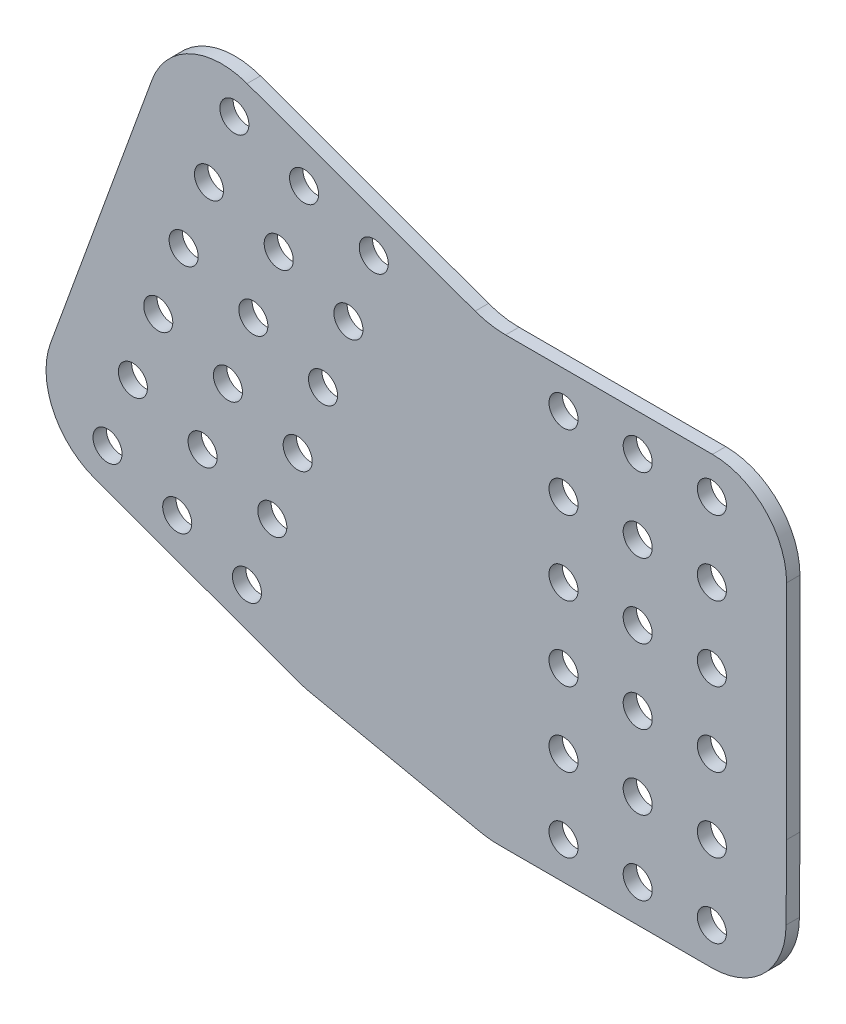
SolidWorks part; units mm, degrees
ref_plane "Front Plane" through (0, 0, 0) normal (0, 0, 1) x (1, 0, 0)
ref_plane "Top Plane" through (0, 0, 0) normal (0, 1, 0) x (1, 0, 0)
ref_plane "Right Plane" through (0, 0, 0) normal (1, 0, 0) x (0, 0, -1)
sketch "Sketch2" plane through (0, 0, 0) normal (0, 0, 1) x (1, 0, 0)
  line L0 (33.4302, 610.9533) -> (33.4302, 560.1533)
  line L1 (33.4302, 610.9533) -> (-17.3698, 610.9533)
  line L2 (-17.3698, 610.9533) -> (-70.8829, 630.4304)
  line L3 (-70.8829, 630.4304) -> (-88.2575, 582.694)
  line L4 (-88.2575, 582.694) -> (-40.5211, 565.3194)
  line L5 (-40.5211, 565.3194) -> (-17.3698, 560.1533)
  line L6 (-17.3698, 560.1533) -> (33.4302, 560.1533)
  line L7 (-70.8829, 630.4304) -> (-76.8499, 632.6022)
  line L8 (-76.8499, 632.6022) -> (-94.2245, 584.8659)
  line L9 (-94.2245, 584.8659) -> (-88.2575, 582.694)
  line L10 (-17.3698, 610.9533) -> (-17.3698, 560.1533)
  line L11 (-40.5211, 565.3194) -> (-23.1465, 613.0558)
  line L12 (33.4302, 610.9533) -> (39.7802, 610.9533)
  line L13 (39.7802, 610.9533) -> (39.7802, 560.1533)
  line L14 (39.7802, 560.1533) -> (33.4302, 560.1533)
  line L15 (-88.2575, 582.694) -> (-92.6011, 570.7599)
  line L16 (-66.5392, 642.3645) -> (-275.0347, 69.5279) construction
  line L17 (-92.6011, 570.7599) -> (-44.8648, 553.3853)
  line L18 (-18.8028, 624.9899) -> (-227.2983, 52.1533) construction
  line L19 (-44.8648, 553.3853) -> (-40.5211, 565.3194)
  line L20 (-17.3698, 560.1533) -> (-17.4643, 547.4533)
  line L21 (-17.4643, 610.9533) -> (-17.4643, -74.8467) construction
  line L22 (-17.4643, 547.4533) -> (33.3357, 547.4533)
  line L23 (33.3357, 610.9533) -> (33.3357, -74.8467) construction
  line L24 (33.3357, 547.4533) -> (33.4302, 560.1533)
  line L25 (-18.8028, 624.9899) -> (-66.5392, 642.3645) construction
  line L26 (-61.1206, 620.1197) -> (-65.4643, 608.1856) construction
  line L27 (-92.6011, 570.7599) -> (-96.9448, 558.8258)
  line L28 (-96.9448, 558.8258) -> (-49.2084, 541.4512)
  line L29 (-49.2084, 541.4512) -> (-44.8648, 553.3853)
  line L30 (-17.4643, 547.4533) -> (-17.4643, 534.7533)
  line L31 (-17.4643, 534.7533) -> (33.3357, 534.7533)
  line L32 (33.3357, 534.7533) -> (33.3357, 547.4533)
  line L33 (-49.2084, 541.4512) -> (-17.4643, 534.7533)
  line L34 (-61.1206, 620.1197) -> (-49.1865, 615.7761) construction
  line L35 (-57.8738, 591.9079) -> (-53.5302, 603.842) construction
  line L36 (-49.1865, 615.7761) -> (-37.2524, 611.4324) construction
  line L37 (-37.2524, 611.4324) -> (-41.5961, 599.4983) construction
  line L38 (-41.5961, 599.4983) -> (-45.9397, 587.5642) construction
  circle A25 centre (-49.1865, 615.7761) radius 2.4892 construction
  circle A26 centre (-61.1206, 620.1197) radius 2.4892 construction
  circle A27 centre (-49.1865, 615.7761) radius 2.4892
  circle A28 centre (-61.1206, 620.1197) radius 2.4892
  circle A29 centre (-37.2524, 611.4324) radius 2.4892 construction
  circle A30 centre (-50.2834, 575.6301) radius 2.4892 construction
  circle A31 centre (-74.1516, 584.3174) radius 2.4892 construction
  circle A32 centre (-62.2175, 579.9738) radius 2.4892 construction
  circle A33 centre (-54.627, 563.696) radius 2.4892 construction
  circle A34 centre (-66.5611, 568.0397) radius 2.4892 construction
  circle A35 centre (-78.4952, 572.3833) radius 2.4892 construction
  circle A36 centre (-37.2524, 611.4324) radius 2.4892
  circle A37 centre (-50.2834, 575.6301) radius 2.4892
  circle A38 centre (-74.1516, 584.3174) radius 2.4892
  circle A39 centre (-62.2175, 579.9738) radius 2.4892
  circle A40 centre (-54.627, 563.696) radius 2.4892
  circle A41 centre (-66.5611, 568.0397) radius 2.4892
  circle A42 centre (-78.4952, 572.3833) radius 2.4892
  circle A43 centre (-4.7643, 591.9033) radius 2.4892 construction
  circle A44 centre (7.9357, 591.9033) radius 2.4892 construction
  circle A45 centre (20.6357, 591.9033) radius 2.4892 construction
  circle A46 centre (20.6357, 604.6033) radius 2.4892 construction
  circle A47 centre (7.9357, 604.6033) radius 2.4892 construction
  circle A48 centre (-4.7643, 604.6033) radius 2.4892 construction
  circle A49 centre (-4.7643, 591.9033) radius 2.4892
  circle A50 centre (7.9357, 591.9033) radius 2.4892
  circle A51 centre (20.6357, 591.9033) radius 2.4892
  circle A52 centre (20.6357, 604.6033) radius 2.4892
  circle A53 centre (7.9357, 604.6033) radius 2.4892
  circle A54 centre (-4.7643, 604.6033) radius 2.4892
  circle A55 centre (20.6357, 553.8033) radius 2.4892 construction
  circle A56 centre (20.6357, 566.5033) radius 2.4892 construction
  circle A57 centre (7.9357, 566.5033) radius 2.4892 construction
  circle A58 centre (-4.7643, 566.5033) radius 2.4892 construction
  circle A59 centre (-4.7643, 579.2033) radius 2.4892 construction
  circle A60 centre (7.9357, 579.2033) radius 2.4892 construction
  circle A61 centre (20.6357, 579.2033) radius 2.4892 construction
  circle A62 centre (20.6357, 553.8033) radius 2.4892
  circle A63 centre (20.6357, 566.5033) radius 2.4892
  circle A64 centre (7.9357, 566.5033) radius 2.4892
  circle A65 centre (-4.7643, 566.5033) radius 2.4892
  circle A66 centre (-4.7643, 579.2033) radius 2.4892
  circle A67 centre (7.9357, 579.2033) radius 2.4892
  circle A68 centre (20.6357, 579.2033) radius 2.4892
  circle A69 centre (20.6357, 541.1033) radius 2.4892 construction
  circle A70 centre (7.9357, 541.1033) radius 2.4892 construction
  circle A71 centre (-4.7643, 541.1033) radius 2.4892 construction
  circle A72 centre (-58.9707, 551.7619) radius 2.4892 construction
  circle A73 centre (-70.9048, 556.1056) radius 2.4892 construction
  circle A74 centre (-82.8389, 560.4492) radius 2.4892 construction
  circle A75 centre (-4.7643, 553.8033) radius 2.4892 construction
  circle A76 centre (7.9357, 553.8033) radius 2.4892 construction
  circle A77 centre (20.6357, 541.1033) radius 2.4892
  circle A78 centre (7.9357, 541.1033) radius 2.4892
  circle A79 centre (-4.7643, 541.1033) radius 2.4892
  circle A80 centre (-58.9707, 551.7619) radius 2.4892
  circle A81 centre (-70.9048, 556.1056) radius 2.4892
  circle A82 centre (-82.8389, 560.4492) radius 2.4892
  circle A83 centre (-4.7643, 553.8033) radius 2.4892
  circle A84 centre (7.9357, 553.8033) radius 2.4892
  circle A85 centre (-65.4643, 608.1856) radius 2.4892
  circle A86 centre (-69.8079, 596.2515) radius 2.4892
  circle A87 centre (-53.5302, 603.842) radius 2.4892
  circle A88 centre (-57.8738, 591.9079) radius 2.4892
  circle A89 centre (-41.5961, 599.4983) radius 2.4892
  circle A90 centre (-45.9397, 587.5642) radius 2.4892
  circle A91 centre (-49.1865, 615.7761) radius 2.4892
  circle A92 centre (-37.2524, 611.4324) radius 2.4892
  point P116 (-53.5302, 603.842)
  point P121 (-41.5961, 599.4983)
  point P122 (-45.9397, 587.5642)
  point P140 (-53.5302, 603.842)
  dimension "D3" = 12.7
  dimension "D6" = 12.7
  dimension "D7" = 3
  dimension "D1" = 50.8
  dimension "D8" = 3
  dimension "D9" = 12.7
  dimension "D10" = 12.7
  dimension "D17" = 50.8
  dimension "D18" = 6.35
  dimension "D19" = 6.35
  dimension "D20" = 6.35
  dimension "D21" = 6.35
  dimension "D22" = 50.8
  dimension "D48" = 12.7
  dimension "D49" = 12.7
  dimension "D50" = 12.7
extrude "Boss-Extrude1" add sketch "Sketch2" along normal blind 2.286 contours L4 L11 L2 L3 | L11 L5 L10 L2 | L1 L10 L6 L0 A41 A39 A37 A28 | L17 L19 L4 L15 A54 A52 | L22 L24 L6 L20 | L28 L29 L17 L27 A82 A81 A80 | L31 L32 L22 L30 A79 A78 A77 | L29 L33 L30 L20 L5 L19 region at (8.0396, 585.5533, 0) region at (32.8584, 553.8072, 0) region at (-25.4909, 582.5086, 0) region at (-31.2956, 549.7891, 0) region at (32.8121, 541.1033, 0) region at (-55.702, 597.8749, 0) region at (-43.2545, 559.5568, 0) region at (-47.5982, 547.6227, 0)
fillet "Fillet6" radius 12.7 4 edges at (-70.8829, 630.4304, 1.143) (-96.9448, 558.8258, 1.143) (33.4302, 610.9533, 1.143) (33.3357, 534.7533, 1.143)
fillet "Fillet7" radius 15.24 3 edges at (-49.2084, 541.4512, 1.143) (-17.4643, 534.7533, 1.143) (-17.3698, 610.9533, 1.143)
